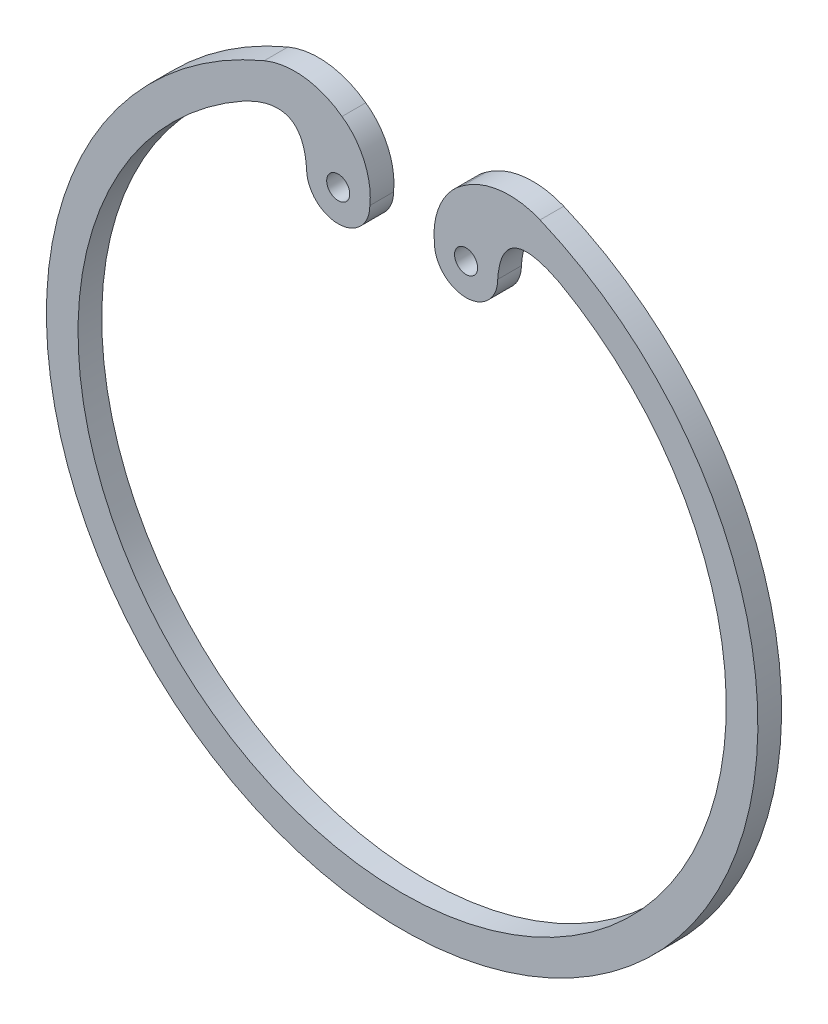
SolidWorks part; units mm, degrees
material "AISI Type A2 Tool Steel"
ref_plane "Front Plane" through (0, 0, 0) normal (0, 0, 1) x (1, 0, 0)
ref_plane "Top Plane" through (0, 0, 0) normal (0, 1, 0) x (1, 0, 0)
ref_plane "Right Plane" through (0, 0, 0) normal (1, 0, 0) x (0, 0, -1)
sketch "Sketch1" plane through (0, 0, 0) normal (0, 0, 1) x (1, 0, 0)
  circle A0 centre (0, 0) radius 41
  circle A1 centre (0, 0) radius 45
  dimension "D1" = 90
  dimension "D2" = 82
extrude "Boss-Extrude1" add sketch "Sketch1" along normal blind 3
sketch "Sketch2" plane through (0, 0, 3) normal (0, 0, 1) x (1, 0, 0)
  line L1 (-15.6689, 42.184) -> (-19.8837, 35.8558)
  arc A4 (-12.0864, 32.285) -> (-4.0864, 32.285) centre (-8.0864, 32.285) ccw
  circle A5 centre (0, 0) radius 41 construction
  circle A6 centre (0, 0) radius 45 construction
  circle A7 centre (-8.0864, 32.285) radius 1.4598
  spline S0 degree 2 poles (-12.0864, 32.285) (-12.5979, 39.5893) (-19.8837, 35.8558) knots 0 0 0 1 1 1
  spline S1 degree 3 poles (-4.0864, 32.285) (-3.7755, 34.9285) (-6.0132, 41.2063) (-12.687, 42.3834) (-15.6689, 42.184) knots 0 0 0 0 0.461233 1 1 1 1
  dimension "D1" = 8
extrude "Boss-Extrude2" add sketch "Sketch2" against normal blind 3
sketch "Sketch3" plane through (0, 0, 3) normal (0, 0, 1) x (1, 0, 0)
  line L0 (0, 45) -> (0, 37.4371)
  line L1 (0, 37.4371) -> (-7.6028, 40.2889)
  line L2 (-7.6028, 40.2889) -> (-11.7167, 43.4479)
  line L3 (-11.7167, 43.4479) -> (-6.5894, 48.4588)
  line L4 (-6.5894, 48.4588) -> (0, 45)
  circle A0 centre (0, 0) radius 45 construction
  circle A1 centre (0, 0) radius 41 construction
  circle A2 centre (0, 0) radius 45 construction
  spline S0 degree 3 poles (-4.0864, 32.285) (-3.7755, 34.9285) (-4.9424, 38.202) (-7.3154, 40.0887) (-7.6028, 40.2889) knots 0 0 0 0 0.461233 0.521445 0.521445 0.521445 0.521445 construction
extrude "Cut-Extrude1" cut sketch "Sketch3" against normal blind 3
fillet "Fillet1" radius 10 1 edges at (-11.7167, 43.4479, 1.5)
mirror "Mirror1" about plane through (0, 0, 0) normal (1, 0, 0) of "Fillet1", "Cut-Extrude1", "Boss-Extrude2"
